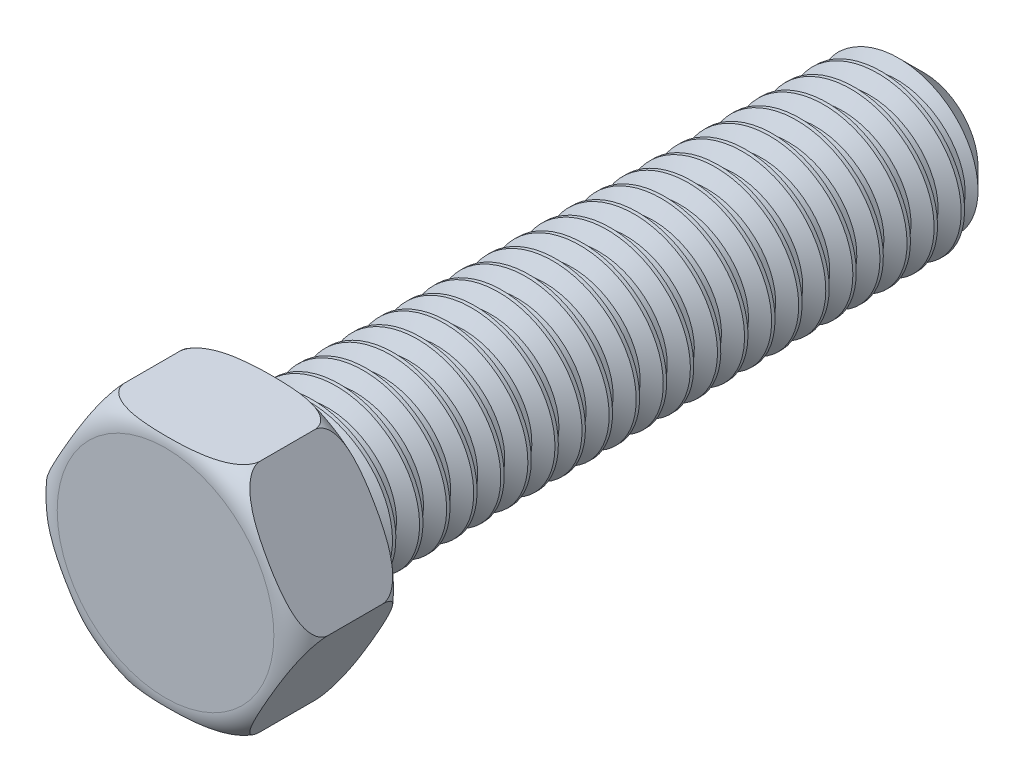
SolidWorks part; units mm, degrees
ref_plane "Front Plane" through (0, 0, 0) normal (0, 0, 1) x (1, 0, 0)
ref_plane "Top Plane" through (0, 0, 0) normal (0, 1, 0) x (1, 0, 0)
ref_plane "Right Plane" through (0, 0, 0) normal (1, 0, 0) x (0, 0, -1)
sketch "Sketch2" plane through (0, 0, 0) normal (0, 0, 1) x (1, 0, 0)
  circle A0 centre (0, 0) radius 2.5
  dimension "D1" = 5
extrude "Boss-Extrude1" add sketch "Sketch2" along normal blind 2
fillet "Fillet1" radius 0.5 2 edges at (2.5, 0, 0) (2.5, 0, 2)
sketch "Sketch3" plane through (0, 0, 2) normal (0, 0, 1) x (1, 0, 0)
  line L1 (2.5, 0) -> (1.25, 2.1651)
  line L2 (1.25, 2.1651) -> (-1.25, 2.1651)
  line L3 (-1.25, 2.1651) -> (-2.5, 0)
  line L4 (-2.5, 0) -> (-1.25, -2.1651)
  line L5 (-1.25, -2.1651) -> (1.25, -2.1651)
  line L6 (1.25, -2.1651) -> (2.5, 0)
  circle A0 centre (0, 0) radius 2.1651 construction
extrude "Cut-Extrude1" cut sketch "Sketch3" against normal through all flip side to cut
sketch "Sketch4" plane through (0, 0, 0) normal (0, 0, -1) x (-1, 0, 0)
  circle A0 centre (0, 0) radius 1.5
  dimension "D1" = 3
extrude "Boss-Extrude2" add sketch "Sketch4" along normal blind 12 separate body
chamfer "Chamfer1" distance 0.5 angle 45 1 edges at (-1.5, 0, -12)
thread "Thread1" pitch 0.5 method cut profile "Thread Profile1" start angle 0, offset 0, length 12, pitch 0.5, diameter 3
ref_plane "Plane1" through (-1.5, 0, 0) normal (0, -1, 0) x (-1, 0, 0)
sketch "Thread Profile1" plane through (-1.5, 0, 0) normal (0, -1, 0) x (-1, 0, 0)
  line L0 (0, 0) -> (0, 0.5) construction
  line L11 (0, 0) -> (0, 0.4375)
  line L12 (0, 0.4375) -> (-0.2706, 0.2812)
  line L13 (-0.2706, 0.2812) -> (-0.2706, 0.1562)
  line L15 (-0.2706, 0.1562) -> (0, 0)
  line L17 (-0.2706, 0.2187) -> (0, 0.2187) construction
  point P2 (0, 0)
  dimension "Pitch" = 0.5
  dimension "Profile_Angle" = 60
  dimension "Profile_Land" = 0.125
  dimension "Profile_Height" = 0.2706
